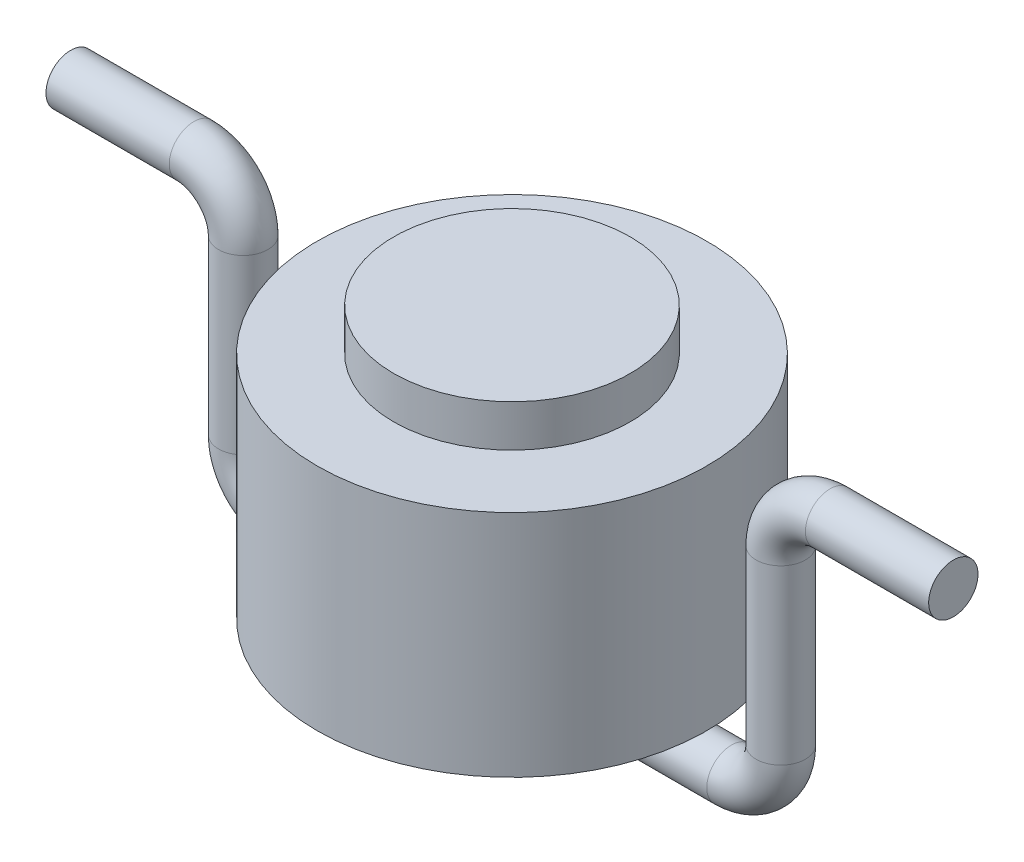
SolidWorks part; units mm, degrees
ref_plane "Front" through (0, 0, 0) normal (0, 0, 1) x (1, 0, 0)
ref_plane "Top" through (0, 0, 0) normal (0, 1, 0) x (1, 0, 0)
ref_plane "Right" through (0, 0, 0) normal (1, 0, 0) x (0, 0, -1)
sketch "Эскиз1" plane through (0, 0, 0) normal (0, 1, 0) x (1, 0, 0)
  circle A0 centre (0, 0) radius 3.95
  circle A1 centre (0, 0) radius 2.4
  dimension "D1" = 7.9
  dimension "D2" = 4.8
extrude "Бобышка-Вытянуть1" add sketch "Эскиз1" along normal blind 4.65 contours A1 | A0 A1 region at (-3.8383, 0, 0) region at (0, 0, 0)
extrude "Бобышка-Вытянуть2" add sketch "Эскиз1<3>" along normal blind 0.85 from surface contours A1 region at (0, 0, 0) starting at face at (0, 4.65, 3.95)
sketch "Эскиз1<3>" plane through (0, 0, 0) normal (0, 1, 0) x (1, 0, 0) same geometry as "Эскиз1"
sketch "Эскиз2" plane through (0, 0, 0) normal (0, 0, 1) x (1, 0, 0)
  line L0 (-8.95, 5) -> (-6.45, 5)
  line L1 (-5.45, 4) -> (-5.45, 0.5)
  line L2 (-4.45, -0.5) -> (4.45, -0.5)
  line L4 (2.4, 5.5) -> (-2.4, 5.5) construction
  line L5 (-3.95, 4.65) -> (-3.95, 0) construction
  line L6 (0, -1.2423) -> (0, 2.2091) construction
  line L7 (-3.95, 0) -> (3.95, 0) construction
  line L8 (5.45, 4) -> (5.45, 0.5)
  line L9 (8.95, 5) -> (6.45, 5)
  arc A0 (-5.45, 0.5) -> (-4.45, -0.5) centre (-4.45, 0.5) ccw
  arc A1 (-6.45, 5) -> (-5.45, 4) centre (-6.45, 4) cw
  arc A2 (6.45, 5) -> (5.45, 4) centre (6.45, 4) ccw
  arc A3 (5.45, 0.5) -> (4.45, -0.5) centre (4.45, 0.5) cw
  point P19 (-5.45, 5)
  point P26 (0, -0.5)
  point P27 (5.45, 5)
  dimension "D5" = 1
  dimension "D1" = 0.5
  dimension "D2" = 1.5
  dimension "D3" = 0.5
  dimension "D4" = 3.5
ref_plane "Плоскость1" through (-8.95, 0, 0) normal (1, 0, 0) x (0, 0, -1)
sketch "Эскиз3" plane through (-8.95, 0, 0) normal (1, 0, 0) x (0, 0, -1)
  circle A0 centre (0, 5) radius 0.5
  dimension "D1" = 1
sweep "По траектории3" add profiles "Эскиз3" path "Эскиз2"
